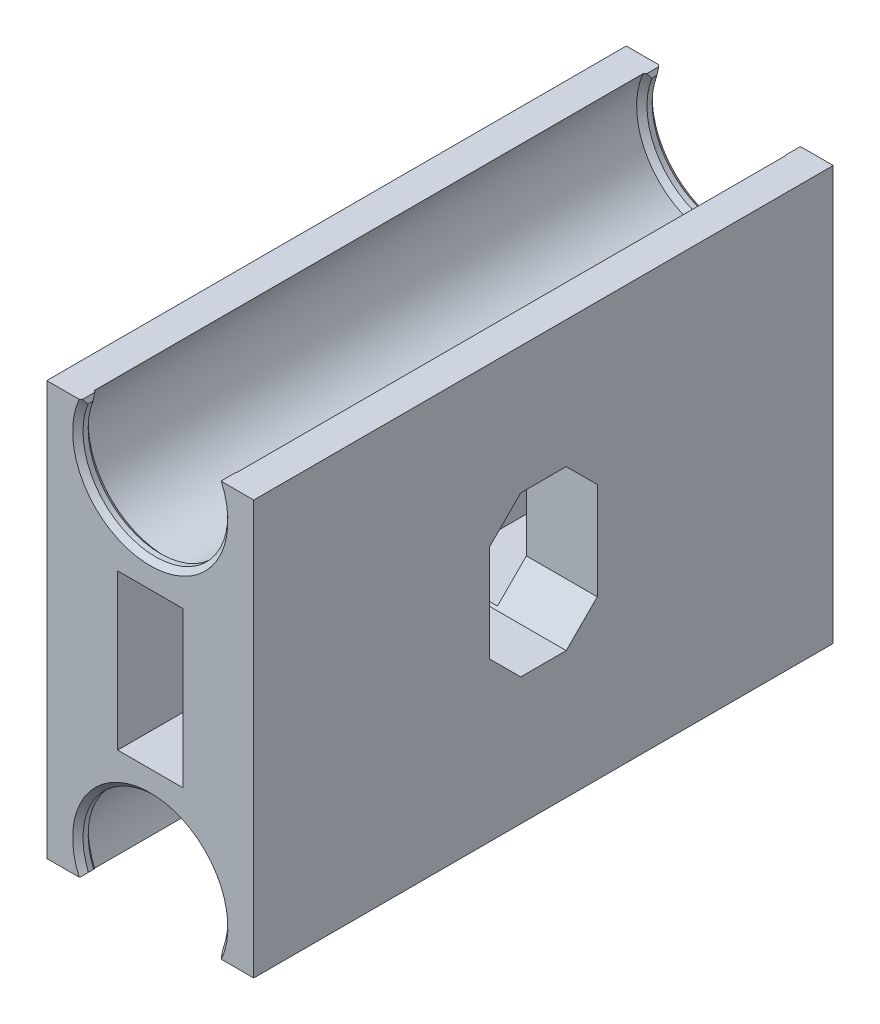
SolidWorks part; units mm, degrees
ref_plane "前视基准面" through (0, 0, 0) normal (0, 0, 1) x (1, 0, 0)
ref_plane "上视基准面" through (0, 0, 0) normal (0, 1, 0) x (1, 0, 0)
ref_plane "右视基准面" through (0, 0, 0) normal (1, 0, 0) x (0, 0, -1)
sketch "草图1" plane through (0, 0, 0) normal (0, 0, 1) x (1, 0, 0)
  line L0 (16.3246, -40) -> (20, -40)
  line L1 (0, 0) -> (3.6754, 0)
  line L2 (0, 0) -> (0, -40)
  line L3 (0, -40) -> (3.6754, -40)
  line L4 (20, 0) -> (20, -40)
  line L5 (16.3246, 0) -> (20, 0)
  line L7 (6.85, -12.5) -> (13.15, -12.5)
  line L8 (6.85, -12.5) -> (6.85, -27.5)
  line L9 (6.85, -27.5) -> (13.15, -27.5)
  line L10 (13.15, -12.5) -> (13.15, -27.5)
  arc A2 (3.6754, 0) -> (16.3246, 0) centre (10, -3) ccw
  arc A3 (16.3246, -40) -> (3.6754, -40) centre (10, -37) ccw
  dimension "D3" = 3
  dimension "D4" = 10
  dimension "D2" = 14
  dimension "D5" = 14
  dimension "D7" = 34
  dimension "D1" = 20
  dimension "D6" = 3
  dimension "D8" = 10
  dimension "D9" = 6.3
  dimension "D10" = 6.85
  dimension "D11" = 15
  dimension "D12" = 9.5
extrude "凸台-拉伸1" add sketch "草图1" along normal blind 56
sketch "草图2" plane through (0, 0, 56) normal (0, 0, 1) x (1, 0, 0)
  circle A0 centre (10, -3) radius 7.5
  circle A1 centre (10, -37) radius 7.5
  dimension "D1" = 15
  dimension "D2" = 15
extrude "切除-拉伸1" cut sketch "草图2" against normal blind 53 from offset 1.5 offset against normal yes
chamfer "倒角1" distance 0.5 angle 45 16 edges at (10, -30, 56) (10, -30, 54.5) (10, -30, 1.5) (10, -30, 0) (10, -10, 1.5) (10, -10, 0) (10, -10, 56) (10, -10, 54.5) (16.3246, 0, 55.25) (16.3246, 0, 0.75) (3.6754, 0, 0.75) (3.6754, 0, 55.25) (3.6754, -40, 0.75) (16.3246, -40, 0.75) (16.3246, -40, 55.25) (3.6754, -40, 55.25)
sketch "草图3" plane through (0, 0, 0) normal (-1, 0, 0) x (0, 0, 1)
  line L0 (56, 0) -> (0, 0) construction
  line L1 (25.8, -12.3) -> (30.2, -12.3)
  line L2 (22.8, -15.3) -> (22.8, -24.7)
  line L3 (25.8, -27.7) -> (30.2, -27.7)
  line L4 (33.2, -15.3) -> (33.2, -24.7)
  line L7 (0, 0) -> (0, -40) construction
  line L9 (22.8, -15.3) -> (25.8, -12.3)
  line L10 (30.2, -12.3) -> (33.2, -15.3)
  line L11 (30.2, -27.7) -> (33.2, -24.7)
  line L12 (22.8, -24.7) -> (25.8, -27.7)
  point P0 (22.8, -12.3)
  point P1 (33.2, -27.7)
  point P2 (22.8, -27.7)
  point P3 (33.2, -12.3)
  dimension "D1" = 10.4
  dimension "D2" = 15.4
  dimension "D3" = 12.3
  dimension "D4" = 22.8
extrude "切除-拉伸5" cut sketch "草图3" against normal blind 57
